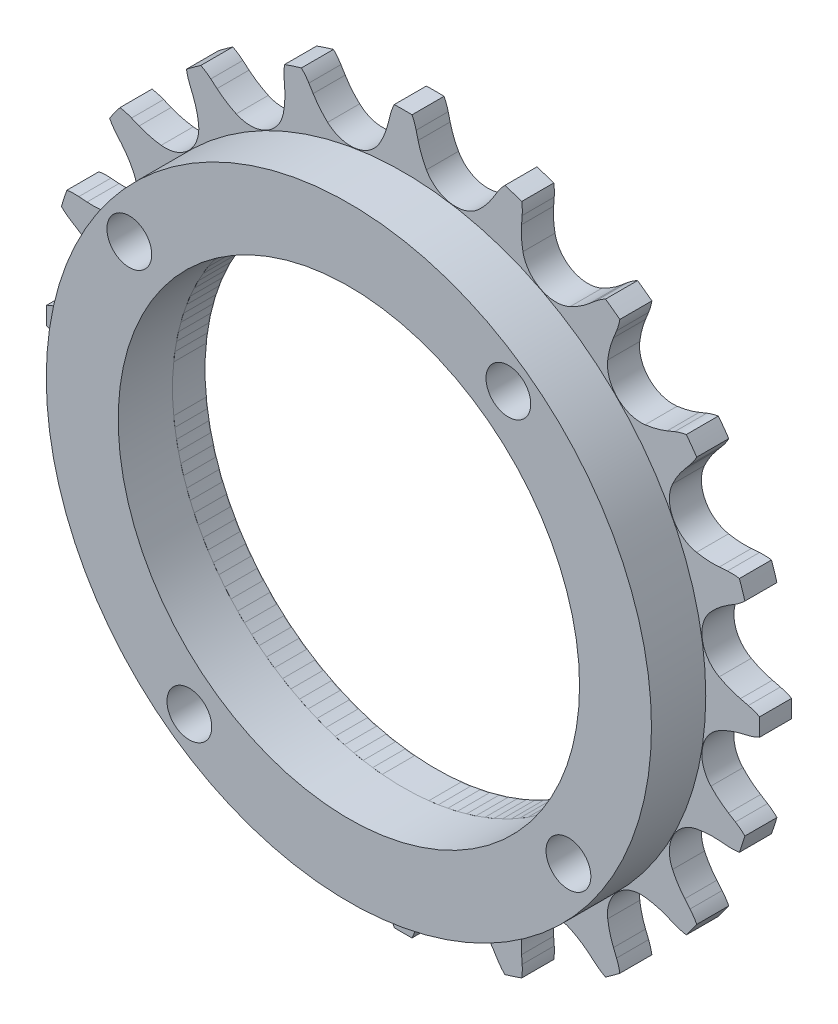
SolidWorks part; units mm, degrees
ref_plane "Front" through (0, 0, 0) normal (0, 0, 1) x (1, 0, 0)
ref_plane "Top" through (0, 0, 0) normal (0, 1, 0) x (1, 0, 0)
ref_plane "Right" through (0, 0, 0) normal (1, 0, 0) x (0, 0, -1)
sketch "Sketch1" plane through (0, 0, 0.25) normal (0, 0, 1) x (1, 0, 0)
  line L0 (-24.4882, 6.9486) -> (-23.9765, 6.6313)
  line L1 (-24.8522, 1.1024) -> (-25.4369, 0.9588)
  line L2 (-25.4369, -0.9588) -> (-24.8522, -1.1024)
  line L3 (-23.9765, -6.6313) -> (-24.4882, -6.9486)
  line L4 (-23.8957, -8.7723) -> (-23.2952, -8.7282)
  line L5 (-20.7538, -13.7159) -> (-21.1425, -14.1758)
  line L6 (-20.0154, -15.7271) -> (-19.4579, -15.4996)
  line L7 (-15.4996, -19.4579) -> (-15.7271, -20.0154)
  line L8 (-14.1758, -21.1425) -> (-13.7159, -20.7538)
  line L9 (-8.7282, -23.2952) -> (-8.7723, -23.8957)
  line L10 (-6.9486, -24.4882) -> (-6.6313, -23.9765)
  line L11 (-1.1024, -24.8522) -> (-0.9588, -25.4369)
  line L12 (0.9588, -25.4369) -> (1.1024, -24.8522)
  line L13 (6.6313, -23.9765) -> (6.9486, -24.4882)
  line L14 (8.7723, -23.8957) -> (8.7282, -23.2952)
  line L15 (13.7159, -20.7538) -> (14.1758, -21.1425)
  line L16 (15.7271, -20.0154) -> (15.4996, -19.4579)
  line L17 (19.4579, -15.4996) -> (20.0154, -15.7271)
  line L18 (21.1425, -14.1758) -> (20.7538, -13.7159)
  line L19 (23.2952, -8.7282) -> (23.8957, -8.7723)
  line L20 (24.4882, -6.9486) -> (23.9765, -6.6313)
  line L21 (24.8522, -1.1024) -> (25.4369, -0.9588)
  line L22 (25.4369, 0.9588) -> (24.8522, 1.1024)
  line L23 (23.9765, 6.6313) -> (24.4882, 6.9486)
  line L24 (23.8957, 8.7723) -> (23.2952, 8.7282)
  line L25 (20.7538, 13.7159) -> (21.1425, 14.1758)
  line L26 (20.0154, 15.7271) -> (19.4579, 15.4996)
  line L27 (15.4996, 19.4579) -> (15.7271, 20.0154)
  line L28 (14.1758, 21.1425) -> (13.7159, 20.7538)
  line L29 (8.7282, 23.2952) -> (8.7723, 23.8957)
  line L30 (6.9486, 24.4882) -> (6.6313, 23.9765)
  line L31 (1.1024, 24.8522) -> (0.9588, 25.4369)
  line L32 (-0.9588, 25.4369) -> (-1.1024, 24.8522)
  line L33 (-6.6313, 23.9765) -> (-6.9486, 24.4882)
  line L34 (-8.7723, 23.8957) -> (-8.7282, 23.2952)
  line L35 (-13.7159, 20.7538) -> (-14.1758, 21.1425)
  line L36 (-15.7271, 20.0154) -> (-15.4996, 19.4579)
  line L37 (-19.4579, 15.4996) -> (-20.0154, 15.7271)
  line L38 (-21.1425, 14.1758) -> (-20.7538, 13.7159)
  line L39 (-23.2952, 8.7282) -> (-23.8957, 8.7723)
  line L40 (6.3855, 9.1279) -> (6.856, 9.5984)
  line L41 (9.5984, 6.856) -> (9.1279, 6.3855)
  line L42 (9.1279, -6.3855) -> (9.5984, -6.856)
  line L43 (6.856, -9.5984) -> (6.3855, -9.1279)
  line L44 (-6.3855, -9.1279) -> (-6.856, -9.5984)
  line L45 (-9.5984, -6.856) -> (-9.1279, -6.3855)
  line L46 (1.9392, 15.5134) -> (1.9392, 10.9696)
  line L47 (-1.9392, 10.9696) -> (-1.9392, 15.5134)
  line L48 (-1.9392, -15.5134) -> (-1.9392, -10.9696)
  line L49 (1.9392, -10.9696) -> (1.9392, -15.5134)
  line L50 (15.5134, -1.9392) -> (10.9696, -1.9392)
  line L51 (10.9696, 1.9392) -> (15.5134, 1.9392)
  line L52 (-15.5134, 1.9392) -> (-10.9696, 1.9392)
  line L53 (-10.9696, -1.9392) -> (-15.5134, -1.9392)
  line L54 (-6.856, 9.5984) -> (-6.3855, 9.1279)
  line L55 (-9.1279, 6.3855) -> (-9.5984, 6.856)
  arc A0 (-25.184, 7.4957) -> (-24.4882, 6.9486) centre (-22.3896, 10.3333) ccw
  arc A1 (-23.9765, 6.6313) -> (-22.6783, 5.565) centre (-27.3234, 1.2333) cw
  arc A2 (-22.6783, 5.565) -> (-23.288, 1.7154) centre (-24.487, 3.8784) cw
  arc A3 (-23.288, 1.7154) -> (-24.8522, 1.1024) centre (-26.3672, 7.2704) cw
  arc A4 (-25.4369, 0.9588) -> (-26.2677, 0.6534) centre (-24.487, -2.9088) ccw
  arc A5 (-26.2677, 0.6534) -> (-26.2677, -0.6534) centre (0, 0) ccw
  arc A6 (-26.2677, -0.6534) -> (-25.4369, -0.9588) centre (-24.487, 2.9088) ccw
  arc A7 (-24.8522, -1.1024) -> (-23.288, -1.7154) centre (-26.3672, -7.2704) cw
  arc A8 (-23.288, -1.7154) -> (-22.6783, -5.565) centre (-24.487, -3.8784) cw
  arc A9 (-22.6783, -5.565) -> (-23.9765, -6.6313) centre (-27.3234, -1.2333) cw
  arc A10 (-24.4882, -6.9486) -> (-25.184, -7.4957) centre (-22.3896, -10.3333) ccw
  arc A11 (-25.184, -7.4957) -> (-24.7802, -8.7386) centre (0, 0) ccw
  arc A12 (-24.7802, -8.7386) -> (-23.8957, -8.7723) centre (-24.1873, -4.8005) ccw
  arc A13 (-23.2952, -8.7282) -> (-21.6181, -8.8278) centre (-22.83, -15.0625) cw
  arc A14 (-21.6181, -8.8278) -> (-19.8487, -12.3006) centre (-22.09, -11.2554) cw
  arc A15 (-19.8487, -12.3006) -> (-20.7538, -13.7159) centre (-25.605, -9.6164) cw
  arc A16 (-21.1425, -14.1758) -> (-21.6351, -14.9112) centre (-18.1006, -16.7463) ccw
  arc A17 (-21.6351, -14.9112) -> (-20.867, -15.9684) centre (0, 0) ccw
  arc A18 (-20.867, -15.9684) -> (-20.0154, -15.7271) centre (-21.5201, -12.0398) ccw
  arc A19 (-19.4579, -15.4996) -> (-17.8321, -15.0761) centre (-17.0581, -21.3802) cw
  arc A20 (-17.8321, -15.0761) -> (-15.0761, -17.8321) centre (-17.5307, -17.5307) cw
  arc A21 (-15.0761, -17.8321) -> (-15.4996, -19.4579) centre (-21.3802, -17.0581) cw
  arc A22 (-15.7271, -20.0154) -> (-15.9684, -20.867) centre (-12.0398, -21.5201) ccw
  arc A23 (-15.9684, -20.867) -> (-14.9112, -21.6351) centre (0, 0) ccw
  arc A24 (-14.9112, -21.6351) -> (-14.1758, -21.1425) centre (-16.7463, -18.1006) ccw
  arc A25 (-13.7159, -20.7538) -> (-12.3006, -19.8487) centre (-9.6164, -25.605) cw
  arc A26 (-12.3006, -19.8487) -> (-8.8278, -21.6181) centre (-11.2554, -22.09) cw
  arc A27 (-8.8278, -21.6181) -> (-8.7282, -23.2952) centre (-15.0625, -22.83) cw
  arc A28 (-8.7723, -23.8957) -> (-8.7386, -24.7802) centre (-4.8005, -24.1873) ccw
  arc A29 (-8.7386, -24.7802) -> (-7.4957, -25.184) centre (0, 0) ccw
  arc A30 (-7.4957, -25.184) -> (-6.9486, -24.4882) centre (-10.3333, -22.3896) ccw
  arc A31 (-6.6313, -23.9765) -> (-5.565, -22.6783) centre (-1.2333, -27.3234) cw
  arc A32 (-5.565, -22.6783) -> (-1.7154, -23.288) centre (-3.8784, -24.487) cw
  arc A33 (-1.7154, -23.288) -> (-1.1024, -24.8522) centre (-7.2704, -26.3672) cw
  arc A34 (-0.9588, -25.4369) -> (-0.6534, -26.2677) centre (2.9088, -24.487) ccw
  arc A35 (-0.6534, -26.2677) -> (0.6534, -26.2677) centre (0, 0) ccw
  arc A36 (0.6534, -26.2677) -> (0.9588, -25.4369) centre (-2.9088, -24.487) ccw
  arc A37 (1.1024, -24.8522) -> (1.7154, -23.288) centre (7.2704, -26.3672) cw
  arc A38 (1.7154, -23.288) -> (5.565, -22.6783) centre (3.8784, -24.487) cw
  arc A39 (5.565, -22.6783) -> (6.6313, -23.9765) centre (1.2333, -27.3234) cw
  arc A40 (6.9486, -24.4882) -> (7.4957, -25.184) centre (10.3333, -22.3896) ccw
  arc A41 (7.4957, -25.184) -> (8.7386, -24.7802) centre (0, 0) ccw
  arc A42 (8.7386, -24.7802) -> (8.7723, -23.8957) centre (4.8005, -24.1873) ccw
  arc A43 (8.7282, -23.2952) -> (8.8278, -21.6181) centre (15.0625, -22.83) cw
  arc A44 (8.8278, -21.6181) -> (12.3006, -19.8487) centre (11.2554, -22.09) cw
  arc A45 (12.3006, -19.8487) -> (13.7159, -20.7538) centre (9.6164, -25.605) cw
  arc A46 (14.1758, -21.1425) -> (14.9112, -21.6351) centre (16.7463, -18.1006) ccw
  arc A47 (14.9112, -21.6351) -> (15.9684, -20.867) centre (0, 0) ccw
  arc A48 (15.9684, -20.867) -> (15.7271, -20.0154) centre (12.0398, -21.5201) ccw
  arc A49 (15.4996, -19.4579) -> (15.0761, -17.8321) centre (21.3802, -17.0581) cw
  arc A50 (15.0761, -17.8321) -> (17.8321, -15.0761) centre (17.5307, -17.5307) cw
  arc A51 (17.8321, -15.0761) -> (19.4579, -15.4996) centre (17.0581, -21.3802) cw
  arc A52 (20.0154, -15.7271) -> (20.867, -15.9684) centre (21.5201, -12.0398) ccw
  arc A53 (20.867, -15.9684) -> (21.6351, -14.9112) centre (0, 0) ccw
  arc A54 (21.6351, -14.9112) -> (21.1425, -14.1758) centre (18.1006, -16.7463) ccw
  arc A55 (20.7538, -13.7159) -> (19.8487, -12.3006) centre (25.605, -9.6164) cw
  arc A56 (19.8487, -12.3006) -> (21.6181, -8.8278) centre (22.09, -11.2554) cw
  arc A57 (21.6181, -8.8278) -> (23.2952, -8.7282) centre (22.83, -15.0625) cw
  arc A58 (23.8957, -8.7723) -> (24.7802, -8.7386) centre (24.1873, -4.8005) ccw
  arc A59 (24.7802, -8.7386) -> (25.184, -7.4957) centre (0, 0) ccw
  arc A60 (25.184, -7.4957) -> (24.4882, -6.9486) centre (22.3896, -10.3333) ccw
  arc A61 (23.9765, -6.6313) -> (22.6783, -5.565) centre (27.3234, -1.2333) cw
  arc A62 (22.6783, -5.565) -> (23.288, -1.7154) centre (24.487, -3.8784) cw
  arc A63 (23.288, -1.7154) -> (24.8522, -1.1024) centre (26.3672, -7.2704) cw
  arc A64 (25.4369, -0.9588) -> (26.2677, -0.6534) centre (24.487, 2.9088) ccw
  arc A65 (26.2677, -0.6534) -> (26.2677, 0.6534) centre (0, 0) ccw
  arc A66 (26.2677, 0.6534) -> (25.4369, 0.9588) centre (24.487, -2.9088) ccw
  arc A67 (24.8522, 1.1024) -> (23.288, 1.7154) centre (26.3672, 7.2704) cw
  arc A68 (23.288, 1.7154) -> (22.6783, 5.565) centre (24.487, 3.8784) cw
  arc A69 (22.6783, 5.565) -> (23.9765, 6.6313) centre (27.3234, 1.2333) cw
  arc A70 (24.4882, 6.9486) -> (25.184, 7.4957) centre (22.3896, 10.3333) ccw
  arc A71 (25.184, 7.4957) -> (24.7802, 8.7386) centre (0, 0) ccw
  arc A72 (24.7802, 8.7386) -> (23.8957, 8.7723) centre (24.1873, 4.8005) ccw
  arc A73 (23.2952, 8.7282) -> (21.6181, 8.8278) centre (22.83, 15.0625) cw
  arc A74 (21.6181, 8.8278) -> (19.8487, 12.3006) centre (22.09, 11.2554) cw
  arc A75 (19.8487, 12.3006) -> (20.7538, 13.7159) centre (25.605, 9.6164) cw
  arc A76 (21.1425, 14.1758) -> (21.6351, 14.9112) centre (18.1006, 16.7463) ccw
  arc A77 (21.6351, 14.9112) -> (20.867, 15.9684) centre (0, 0) ccw
  arc A78 (20.867, 15.9684) -> (20.0154, 15.7271) centre (21.5201, 12.0398) ccw
  arc A79 (19.4579, 15.4996) -> (17.8321, 15.0761) centre (17.0581, 21.3802) cw
  arc A80 (17.8321, 15.0761) -> (15.0761, 17.8321) centre (17.5307, 17.5307) cw
  arc A81 (15.0761, 17.8321) -> (15.4996, 19.4579) centre (21.3802, 17.0581) cw
  arc A82 (15.7271, 20.0154) -> (15.9684, 20.867) centre (12.0398, 21.5201) ccw
  arc A83 (15.9684, 20.867) -> (14.9112, 21.6351) centre (0, 0) ccw
  arc A84 (14.9112, 21.6351) -> (14.1758, 21.1425) centre (16.7463, 18.1006) ccw
  arc A85 (13.7159, 20.7538) -> (12.3006, 19.8487) centre (9.6164, 25.605) cw
  arc A86 (12.3006, 19.8487) -> (8.8278, 21.6181) centre (11.2554, 22.09) cw
  arc A87 (8.8278, 21.6181) -> (8.7282, 23.2952) centre (15.0625, 22.83) cw
  arc A88 (8.7723, 23.8957) -> (8.7386, 24.7802) centre (4.8005, 24.1873) ccw
  arc A89 (8.7386, 24.7802) -> (7.4957, 25.184) centre (0, 0) ccw
  arc A90 (7.4957, 25.184) -> (6.9486, 24.4882) centre (10.3333, 22.3896) ccw
  arc A91 (6.6313, 23.9765) -> (5.565, 22.6783) centre (1.2333, 27.3234) cw
  arc A92 (5.565, 22.6783) -> (1.7154, 23.288) centre (3.8784, 24.487) cw
  arc A93 (1.7154, 23.288) -> (1.1024, 24.8522) centre (7.2704, 26.3672) cw
  arc A94 (0.9588, 25.4369) -> (0.6534, 26.2677) centre (-2.9088, 24.487) ccw
  arc A95 (0.6534, 26.2677) -> (-0.6534, 26.2677) centre (0, 0) ccw
  arc A96 (-0.6534, 26.2677) -> (-0.9588, 25.4369) centre (2.9088, 24.487) ccw
  arc A97 (-1.1024, 24.8522) -> (-1.7154, 23.288) centre (-7.2704, 26.3672) cw
  arc A98 (-1.7154, 23.288) -> (-5.565, 22.6783) centre (-3.8784, 24.487) cw
  arc A99 (-5.565, 22.6783) -> (-6.6313, 23.9765) centre (-1.2333, 27.3234) cw
  arc A100 (-6.9486, 24.4882) -> (-7.4957, 25.184) centre (-10.3333, 22.3896) ccw
  arc A101 (-7.4957, 25.184) -> (-8.7386, 24.7802) centre (0, 0) ccw
  arc A102 (-8.7386, 24.7802) -> (-8.7723, 23.8957) centre (-4.8005, 24.1873) ccw
  arc A103 (-8.7282, 23.2952) -> (-8.8278, 21.6181) centre (-15.0625, 22.83) cw
  arc A104 (-8.8278, 21.6181) -> (-12.3006, 19.8487) centre (-11.2554, 22.09) cw
  arc A105 (-12.3006, 19.8487) -> (-13.7159, 20.7538) centre (-9.6164, 25.605) cw
  arc A106 (-14.1758, 21.1425) -> (-14.9112, 21.6351) centre (-16.7463, 18.1006) ccw
  arc A107 (-14.9112, 21.6351) -> (-15.9684, 20.867) centre (0, 0) ccw
  arc A108 (-15.9684, 20.867) -> (-15.7271, 20.0154) centre (-12.0398, 21.5201) ccw
  arc A109 (-15.4996, 19.4579) -> (-15.0761, 17.8321) centre (-21.3802, 17.0581) cw
  arc A110 (-15.0761, 17.8321) -> (-17.8321, 15.0761) centre (-17.5307, 17.5307) cw
  arc A111 (-17.8321, 15.0761) -> (-19.4579, 15.4996) centre (-17.0581, 21.3802) cw
  arc A112 (-20.0154, 15.7271) -> (-20.867, 15.9684) centre (-21.5201, 12.0398) ccw
  arc A113 (-20.867, 15.9684) -> (-21.6351, 14.9112) centre (0, 0) ccw
  arc A114 (-21.6351, 14.9112) -> (-21.1425, 14.1758) centre (-18.1006, 16.7463) ccw
  arc A115 (-20.7538, 13.7159) -> (-19.8487, 12.3006) centre (-25.605, 9.6164) cw
  arc A116 (-19.8487, 12.3006) -> (-21.6181, 8.8278) centre (-22.09, 11.2554) cw
  arc A117 (-21.6181, 8.8278) -> (-23.2952, 8.7282) centre (-22.83, 15.0625) cw
  arc A118 (-23.8957, 8.7723) -> (-24.7802, 8.7386) centre (-24.1873, 4.8005) ccw
  arc A119 (-24.7802, 8.7386) -> (-25.184, 7.4957) centre (0, 0) ccw
  circle A120 centre (0, 0) radius 6.7871
  arc A121 (9.1279, 6.3855) -> (6.3855, 9.1279) centre (7.7567, 7.7567) cw
  arc A122 (6.856, 9.5984) -> (9.5984, 6.856) centre (8.2272, 8.2272) cw
  arc A123 (6.3855, -9.1279) -> (9.1279, -6.3855) centre (7.7567, -7.7567) cw
  arc A124 (9.5984, -6.856) -> (6.856, -9.5984) centre (8.2272, -8.2272) cw
  arc A125 (-9.1279, -6.3855) -> (-6.3855, -9.1279) centre (-7.7567, -7.7567) cw
  arc A126 (-6.856, -9.5984) -> (-9.5984, -6.856) centre (-8.2272, -8.2272) cw
  arc A127 (1.9392, 10.9696) -> (-1.9392, 10.9696) centre (0, 10.9696) cw
  arc A128 (-1.9392, 15.5134) -> (1.9392, 15.5134) centre (0, 15.5134) cw
  arc A129 (-1.9392, -10.9696) -> (1.9392, -10.9696) centre (0, -10.9696) cw
  arc A130 (1.9392, -15.5134) -> (-1.9392, -15.5134) centre (0, -15.5134) cw
  arc A131 (10.9696, -1.9392) -> (10.9696, 1.9392) centre (10.9696, 0) cw
  arc A132 (15.5134, 1.9392) -> (15.5134, -1.9392) centre (15.5134, 0) cw
  arc A133 (-10.9696, 1.9392) -> (-10.9696, -1.9392) centre (-10.9696, 0) cw
  arc A134 (-15.5134, -1.9392) -> (-15.5134, 1.9392) centre (-15.5134, 0) cw
  arc A135 (-6.3855, 9.1279) -> (-9.1279, 6.3855) centre (-7.7567, 7.7567) cw
  arc A136 (-9.5984, 6.856) -> (-6.856, 9.5984) centre (-8.2272, 8.2272) cw
extrude "Boss-Extrude1" add sketch "Sketch1" against normal blind 2.3622
sketch "Sketch2" plane through (0, 0, 0.25) normal (0, 0, 1) x (1, 0, 0)
  circle A0 centre (0, 0) radius 18
extrude "Boss-Extrude2" add sketch "Sketch2" against normal blind 2.4 separate body
sketch "Sketch3" plane through (0, 0, 0.25) normal (0, 0, 1) x (1, 0, 0)
  circle A0 centre (0, 0) radius 17
extrude "Cut-Extrude1" cut sketch "Sketch3" against normal blind 2.4
sketch "Sketch6" plane through (0, 0, 0.25) normal (0, 0, 1) x (1, 0, 0)
  circle A0 centre (0, 0) radius 17
  circle A1 centre (0, 0) radius 22.3005
extrude "Boss-Extrude3" add sketch "Sketch6" along normal blind 4 separate body
sketch "Sketch5" plane through (0, 0, -2.1122) normal (0, 0, -1) x (-1, 0, 0)
  line L0 (21.2576, 15.4446) -> (13.7533, 9.9923)
  arc A0 (21.6351, 14.9112) -> (20.867, 15.9684) centre (0, 0) ccw construction
  circle A1 centre (0, 0) radius 17 construction
  circle A2 centre (16.1803, 11.7557) radius 1.65
  circle A3 centre (16.1803, 11.7557) radius 3
  circle A4 centre (11.7557, -16.1803) radius 1.65
  circle A5 centre (-16.1803, -11.7557) radius 1.65
  circle A6 centre (-11.7557, 16.1803) radius 1.65
  point P20 (0, 0)
  dimension "D1" = 3
  dimension "D2" = 4
extrude "Cut-Extrude3" cut sketch "Sketch5" against normal through all contours L0 A2 | L0 A2 | A4 | A5 | A6 region at (-16.592, 11.1892, -2.1122) region at (-15.7687, 12.3222, -2.1122) region at (-11.7557, -16.1803, -2.1122) region at (16.1803, -11.7557, -2.1122) region at (11.7557, 16.1803, -2.1122)
sketch "Sketch7" plane through (0, 0, 4.25) normal (0, 0, 1) x (1, 0, 0)
  circle A0 centre (11.7557, 16.1803) radius 3.75
  circle A1 centre (16.1803, -11.7557) radius 3.75
  circle A2 centre (-11.7557, -16.1803) radius 3.75
  circle A3 centre (-16.1803, 11.7557) radius 3.75
  point P12 (0, 0)
  dimension "D1" = 4
extrude "Cut-Extrude4" [suppressed] cut sketch "Sketch7" against normal blind 3
sketch "Sketch8" [suppressed] plane through (0, 0, 1.25) normal (0, 0, 1) x (1, 0, 0)
  circle A0 centre (11.7557, 16.1803) radius 3.5
extrude "Boss-Extrude4" [suppressed] add sketch "Sketch8" along normal blind 2.8
